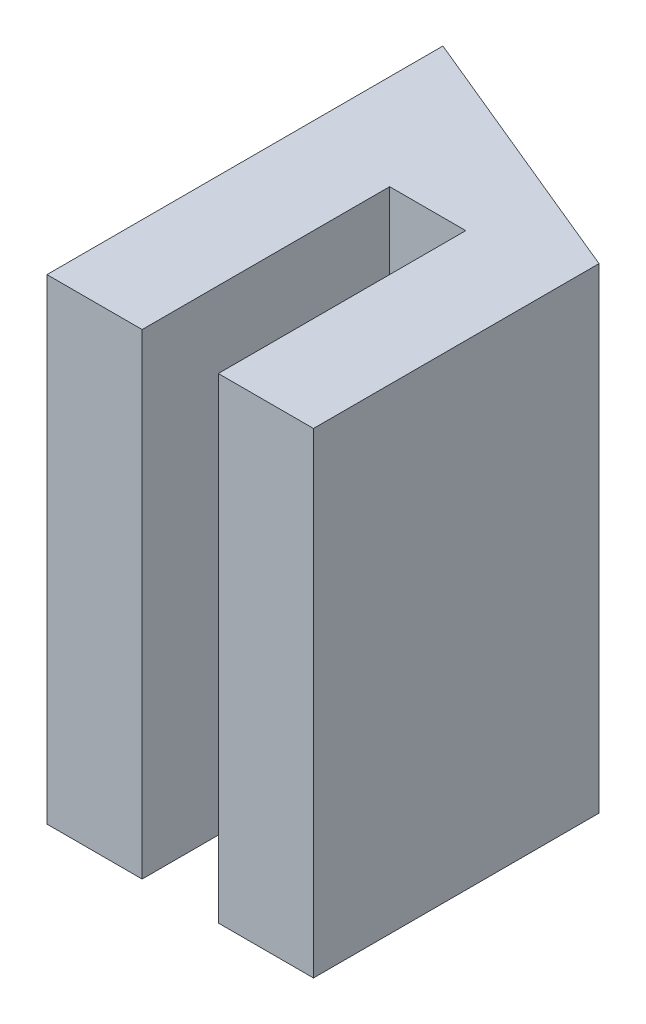
SolidWorks part; units mm, degrees
ref_plane "Front Plane" through (0, 0, 0) normal (0, 0, 1) x (1, 0, 0)
ref_plane "Top Plane" through (0, 0, 0) normal (0, 1, 0) x (1, 0, 0)
ref_plane "Right Plane" through (0, 0, 0) normal (1, 0, 0) x (0, 0, -1)
sketch "Sketch2" plane through (0, 0, 0) normal (0, 1, 0) x (1, 0, 0)
  line L0 (0, 0) -> (0, -15)
  line L1 (0, -15) -> (-5, -15)
  line L2 (-5, -15) -> (-5, -2)
  line L3 (-5, -2) -> (-9, -2)
  line L4 (-9, -2) -> (-9, -15)
  line L5 (-9, -15) -> (-14, -15)
  line L6 (0, 0) -> (-14, 5.799)
  line L7 (-14, -15) -> (-14, 5.799)
  point P8 (-0.3121, 0.1293)
  point P11 (0, 0)
  point P12 (0, 0)
  point P13 (0, 0)
  point P14 (0, 0)
  point P15 (0, 0)
  point P16 (0, 0)
  point P17 (0, 0)
  point P18 (-14, 5.799)
  point P19 (-14.1848, 5.799)
extrude "Boss-Extrude1" add sketch "Sketch2" along normal blind 25
